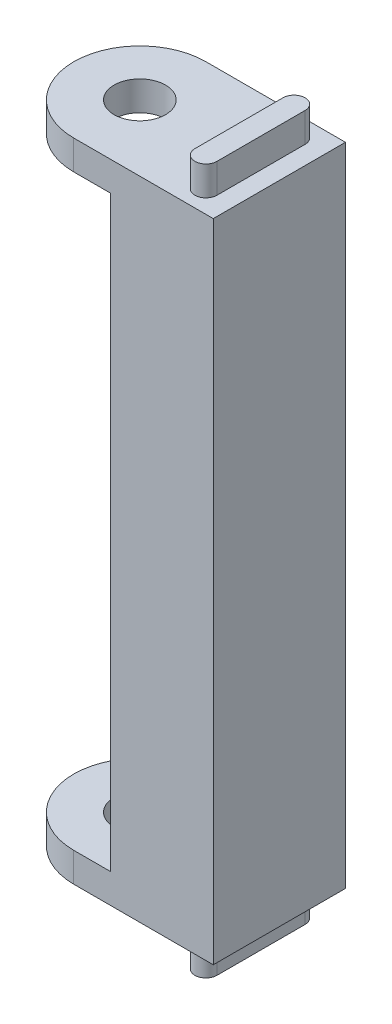
SolidWorks part; units mm, degrees
ref_plane "Front Plane" through (0, 0, 0) normal (0, 0, 1) x (1, 0, 0)
ref_plane "Top Plane" through (0, 0, 0) normal (0, 1, 0) x (1, 0, 0)
ref_plane "Right Plane" through (0, 0, 0) normal (1, 0, 0) x (0, 0, -1)
sketch "Sketch1" plane through (0, 0, 0) normal (0, 1, 0) x (1, 0, 0)
  line L0 (-2.5, 0) -> (2.5, 0) construction
  line L5 (-2.5, 4.5) -> (2.509, 4.5)
  line L6 (-2.5, -4.5) -> (2.509, -4.5)
  line L8 (7, -4.5) -> (7, 4.5)
  line L10 (7, 4.5) -> (2.509, 4.5)
  line L12 (7, -4.5) -> (7, 4.5)
  line L14 (7, -4.5) -> (2.509, -4.5)
  line L15 (5, 3) -> (5, -3) construction
  line L16 (5.75, 3) -> (5.75, -3)
  line L17 (4.25, 3) -> (4.25, -3)
  arc A1 (-2.5, 4.5) -> (-2.5, -4.5) centre (-2.5, 0) ccw
  circle A3 centre (-2.5, 0) radius 1.75
  arc A4 (0.0045, 4.5) -> (0.0045, -4.5) centre (-2.5, 0) cw
  arc A5 (5.75, 3) -> (4.25, 3) centre (5, 3) ccw
  arc A6 (4.25, -3) -> (5.75, -3) centre (5, -3) ccw
  point P2 (0, 0)
  point P7 (5, 0)
  point P21 (0, 0)
  point P22 (7, 0)
  point P23 (5, 0)
  point P24 (0, 0)
  point P25 (-7, 0)
  dimension "D2" = 9.5
  dimension "D3" = 3.5
  dimension "D6" = 5.15
  dimension "D8" = 1.5
  dimension "D9" = 6
  dimension "D10" = 14
  dimension "D1" = 9
  dimension "D4" = 5
  dimension "D5" = 2.5
  dimension "D7" = 2
extrude "Boss-Extrude3" add sketch "Sketch1" along normal blind 2 contours A4 L5 A1 L6 A3 | L5 A4 L6 L14 L8 L10 A6 L17 A5 L16 | L17 A6 L16 A5 region at (-1.2478, 0, -4.368) region at (4.2023, 0, 0) region at (5, 0, 0)
extrude "Boss-Extrude4" add sketch "Sketch1<3>" against normal blind 20 contours L5 A4 L6 L14 L8 L10 A6 L17 A5 L16 | L17 A6 L16 A5
sketch "Sketch1<3>" plane through (0, 0, 0) normal (0, 1, 0) x (1, 0, 0) same geometry as "Sketch1"
extrude "Boss-Extrude5" add sketch "Sketch1<5>" along normal blind 4 contours L17 A6 L16 A5 region at (5, 0, 0)
sketch "Sketch1<5>" plane through (0, 0, 0) normal (0, 1, 0) x (1, 0, 0) same geometry as "Sketch1"
mirror "Mirror1" about plane through (0, -20, 0) normal (0, 1, 0) of bodies 111
